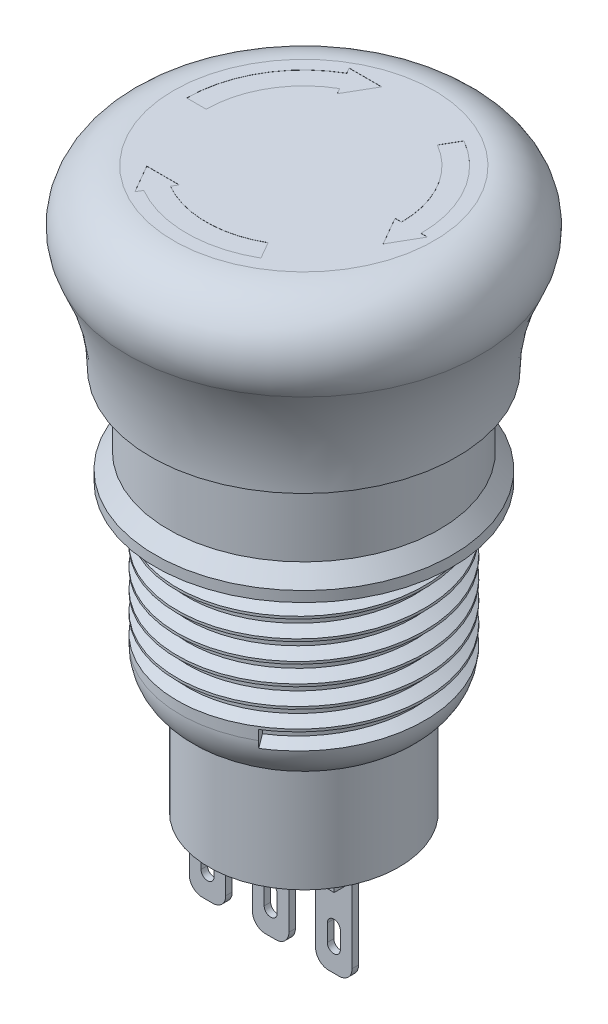
SolidWorks part; units mm, degrees
ref_plane "Front Plane" through (0, 0, 0) normal (0, 0, 1) x (1, 0, 0)
ref_plane "Top Plane" through (0, 0, 0) normal (0, 1, 0) x (1, 0, 0)
ref_plane "Right Plane" through (0, 0, 0) normal (1, 0, 0) x (0, 0, -1)
sketch "Sketch1" plane through (0, 0, 0) normal (0, 0, 1) x (1, 0, 0)
  line L0 (0, 0) -> (-11.75, 0)
  line L1 (-10, 13.5) -> (0, 13.5)
  line L2 (0, 13.5) -> (0, 0)
  arc A0 (-11.75, 0) -> (-13.5751, 7.7059) centre (-28.9306, 0) ccw
  arc A1 (-13.5751, 7.7059) -> (-10, 13.5) centre (-10, 9.5) cw
  dimension "D4" = 14
  dimension "D1" = 10
  dimension "D2" = 13.5
  dimension "D3" = 11.75
revolve "Revolve1" add sketch "Sketch1" angle 360 about L2
sketch "Sketch2" plane through (0, 0, 0) normal (0, 0, 1) x (1, 0, 0)
  line L0 (0, 0) -> (-10.4, 0)
  line L1 (-11.75, 0) -> (11.75, 0) construction
  line L2 (-10.4, 0) -> (-10.4, -5.5)
  line L3 (-10.4, -5.5) -> (-11.4, -6.7)
  line L5 (-9.5, -7.5) -> (-9.5, -21.5)
  line L7 (0, -21.5) -> (0, 0)
  line L8 (-11.4, -6.7) -> (-11.4, -7.5)
  line L9 (-11.4, -7.5) -> (-9.5, -7.5)
  line L12 (-9.5, -21.5) -> (0, -21.5)
  dimension "D1" = 10.4
  dimension "D2" = 11.4
  dimension "D3" = 2
  dimension "D4" = 5.5
  dimension "D5" = 0.8
  dimension "D6" = 9.5
  dimension "D7" = 14
revolve "Revolve2" add sketch "Sketch2" angle 360 about L7
sketch "Sketch5" plane through (0, -21.5, 0) normal (0, -1, 0) x (1, 0, 0)
  circle A0 centre (0, 0) radius 7.3
  dimension "D1" = 14.6
extrude "Boss-Extrude1" add sketch "Sketch5" along normal blind 8
sketch "Sketch6" plane through (0, -29.5, 0) normal (0, -1, 0) x (1, 0, 0)
  line L0 (0, 2.3) -> (0, 0) construction
  line L1 (-6, 3.675) -> (6, 3.675)
  line L2 (-6, 3.675) -> (-6, 0.925)
  line L3 (-6, 0.925) -> (6, 0.925)
  line L4 (6, 3.675) -> (6, 0.925)
  line L5 (-6, 3.675) -> (6, 0.925) construction
  line L6 (-6, 0.925) -> (6, 3.675) construction
  line L7 (0, 0) -> (0, 7.3) construction
  circle A1 centre (0, 0) radius 7.3 construction
  point P0 (0, 2.3)
  dimension "D1" = 2.75
  dimension "D2" = 12
  dimension "D3" = 5
sketch "Sketch7" plane through (0, -29.5, 0) normal (0, -1, 0) x (1, 0, 0)
  line L0 (-4.85, 2.3) -> (0, 2.3) construction
  line L1 (-6.25, 2.55) -> (-3.45, 2.55)
  line L2 (-6.25, 2.55) -> (-6.25, 2.05)
  line L3 (-6.25, 2.05) -> (-3.45, 2.05)
  line L4 (-3.45, 2.55) -> (-3.45, 2.05)
  line L5 (-6.25, 2.55) -> (-3.45, 2.05) construction
  line L6 (-6.25, 2.05) -> (-3.45, 2.55) construction
  line L7 (-1.4, 2.55) -> (1.4, 2.55)
  line L8 (-1.4, 2.55) -> (-1.4, 2.05)
  line L9 (-1.4, 2.05) -> (1.4, 2.05)
  line L10 (1.4, 2.55) -> (1.4, 2.05)
  line L11 (-1.4, 2.55) -> (1.4, 2.05) construction
  line L12 (-1.4, 2.05) -> (1.4, 2.55) construction
  line L13 (3.45, 2.55) -> (6.25, 2.55)
  line L14 (3.45, 2.55) -> (3.45, 2.05)
  line L15 (3.45, 2.05) -> (6.25, 2.05)
  line L16 (6.25, 2.55) -> (6.25, 2.05)
  line L17 (3.45, 2.55) -> (6.25, 2.05) construction
  line L18 (3.45, 2.05) -> (6.25, 2.55) construction
  line L19 (0, 2.3) -> (4.85, 2.3) construction
  line L20 (0, 0) -> (0, 7.3) construction
  circle A3 centre (0, 0) radius 7.3
  circle A4 centre (0, 0) radius 7.3 construction
  point P0 (-4.85, 2.3)
  point P5 (0, 2.3)
  point P10 (4.85, 2.3)
  dimension "D1" = 2.8
  dimension "D2" = 0.5
  dimension "D3" = 0
  dimension "D4" = 4.85
  dimension "D5" = 5
extrude "Boss-Extrude3" add sketch "Sketch7" along normal blind 7 contours L8 L7 L10 L9 | L2 L1 L4 L3 | L14 L13 L16 L15
sketch "Sketch8" plane through (0, 0, 2.05) normal (0, 0, -1) x (-1, 0, 0)
  line L0 (-4.85, -33.4) -> (-4.85, -34.7) construction
  line L1 (-4.35, -33.4) -> (-4.35, -34.7)
  line L2 (-5.35, -33.4) -> (-5.35, -34.7)
  line L3 (0, -33.4) -> (0, -34.7) construction
  line L4 (0.5, -33.4) -> (0.5, -34.7)
  line L5 (-0.5, -33.4) -> (-0.5, -34.7)
  line L6 (4.85, -33.4) -> (4.85, -34.7) construction
  line L7 (5.35, -33.4) -> (5.35, -34.7)
  line L8 (4.35, -33.4) -> (4.35, -34.7)
  line L9 (-4.85, -34.05) -> (0, -34.05) construction
  line L10 (0, -34.05) -> (4.85, -34.05) construction
  line L14 (-4.85, -34.7) -> (-4.85, -35.2) construction
  line L16 (-3.45, -36.5) -> (-6.25, -36.5) construction
  arc A0 (-4.35, -33.4) -> (-5.35, -33.4) centre (-4.85, -33.4) ccw
  arc A1 (-5.35, -34.7) -> (-4.35, -34.7) centre (-4.85, -34.7) ccw
  arc A2 (0.5, -33.4) -> (-0.5, -33.4) centre (0, -33.4) ccw
  arc A3 (-0.5, -34.7) -> (0.5, -34.7) centre (0, -34.7) ccw
  arc A4 (5.35, -33.4) -> (4.35, -33.4) centre (4.85, -33.4) ccw
  arc A5 (4.35, -34.7) -> (5.35, -34.7) centre (4.85, -34.7) ccw
  point P2 (-4.85, -34.05)
  point P7 (0, -34.05)
  point P15 (4.85, -34.05)
  dimension "D1" = 2.3
  dimension "D3" = 1.3
  dimension "D4" = 0.5
  dimension "D2" = 1
  dimension "D5" = 1
extrude "Cut-Extrude1" cut sketch "Sketch8" against normal up to next
sketch "Sketch10" plane through (0, -29.5, 0) normal (0, -1, 0) x (1, 0, 0)
  line L0 (-5.6941, 0.6706) -> (-5.6941, -2.6706) construction
  line L1 (-0.8, 0.6706) -> (-0.8, -2.6706) construction
  line L2 (4.1319, 0.6706) -> (4.1319, -2.6706) construction
  line L3 (4.1319, -2.6706) -> (-0.8, -2.6706) construction
  line L4 (-0.8, -2.6706) -> (-5.6941, -2.6706) construction
  line L5 (0, 2.05) -> (0, 0) construction
  line L7 (-0.8, -1) -> (0.8, -1) construction
  line L8 (-1.4, 2.05) -> (1.4, 2.05) construction
  line L9 (0, 0) -> (0, -1) construction
  text T0 "NC" font "Century Gothic" height in points 6
  text T1 "NO" font "Century Gothic" height in points 6
  text T2 "C" font "Century Gothic" height in points 7
  dimension "D1" = 1.6
  dimension "D2" = 1
extrude "Boss-Extrude4" add sketch "Sketch10" along normal blind 0.1
extrude "Yükseklik-Ekstrüzyon1" add sketch "Sketch6" along normal blind 0.5
fillet "Radyus1" radius 1 6 edges at (6.25, -36.5, 2.3) (3.45, -36.5, 2.3) (1.4, -36.5, 2.3) (-1.4, -36.5, 2.3) (-3.45, -36.5, 2.3) (-6.25, -36.5, 2.3)
fillet "Radyus2" radius 3.5 1 edges at (0, -21.5, -9.5)
sketch "Çizim1" plane through (0, 13.5, 0) normal (0, 1, 0) x (1, 0, 0)
  line L0 (-9, 0) -> (-7.5, 0)
  line L1 (0, 0) -> (-3.75, 6.4952) construction
  line L3 (-4.75, 8.2272) -> (-2.25, 8.2272)
  line L4 (-2.25, 8.2272) -> (-3.5, 6.0622)
  line L5 (-3.5, 6.0622) -> (-3.75, 6.4952)
  line L6 (-4.5, 7.7942) -> (-4.75, 8.2272)
  line L7 (4.5, 7.7942) -> (3.75, 6.4952)
  line L8 (7, 0) -> (7.5, 0)
  line L9 (8.25, -2.1651) -> (7, 0)
  line L10 (9.5, 0) -> (8.25, -2.1651)
  line L11 (9, 0) -> (9.5, 0)
  line L12 (4.5, -7.7942) -> (3.75, -6.4952)
  line L13 (-3.5, -6.0622) -> (-3.75, -6.4952)
  line L14 (-6, -6.0622) -> (-3.5, -6.0622)
  line L15 (-4.75, -8.2272) -> (-6, -6.0622)
  line L16 (-4.5, -7.7942) -> (-4.75, -8.2272)
  arc A0 (-3.75, 6.4952) -> (-7.5, 0) centre (0, 0) ccw
  arc A1 (-4.5, 7.7942) -> (-9, 0) centre (0, 0) ccw
  circle A2 centre (0, 0) radius 1.5197 construction
  arc A3 (9, 0) -> (4.5, 7.7942) centre (0, 0) ccw
  arc A4 (7.5, 0) -> (3.75, 6.4952) centre (0, 0) ccw
  arc A5 (-4.5, -7.7942) -> (4.5, -7.7942) centre (0, 0) ccw
  arc A6 (-3.75, -6.4952) -> (3.75, -6.4952) centre (0, 0) ccw
  point P1 (-4.125, 7.1447)
  dimension "D1" = 1.5
  dimension "D2" = 15
  dimension "D3" = 60
  dimension "D4" = 2.5
  dimension "D5" = 3
extrude "Kes-Ekstrüzyon1" cut sketch "Çizim1" against normal blind 0.01
thread "Diş1" pitch 1.5 method cut profile "Diş Profili1" start angle 0, offset 0, length 10, pitch 1.5, diameter 19
ref_plane "Düzlem1" through (-9.5, -7.5, 0) normal (0, 0, 1) x (-1, 0, 0)
sketch "Diş Profili1" plane through (-9.5, -7.5, 0) normal (0, 0, 1) x (-1, 0, 0)
  line L0 (0, 0) -> (0, 1.5) construction
  line L11 (0, 0) -> (0, 1.3125)
  line L12 (0, 1.3125) -> (-0.8119, 0.8437)
  line L13 (-0.8119, 0.8437) -> (-0.8119, 0.4687)
  line L15 (-0.8119, 0.4687) -> (0, 0)
  line L17 (-0.8119, 0.6562) -> (0, 0.6562) construction
  point P2 (0, 0)
  dimension "Pitch" = 1.5
  dimension "Profile_Angle" = 60
  dimension "Profile_Land" = 0.375
  dimension "Profile_Height" = 0.8119
